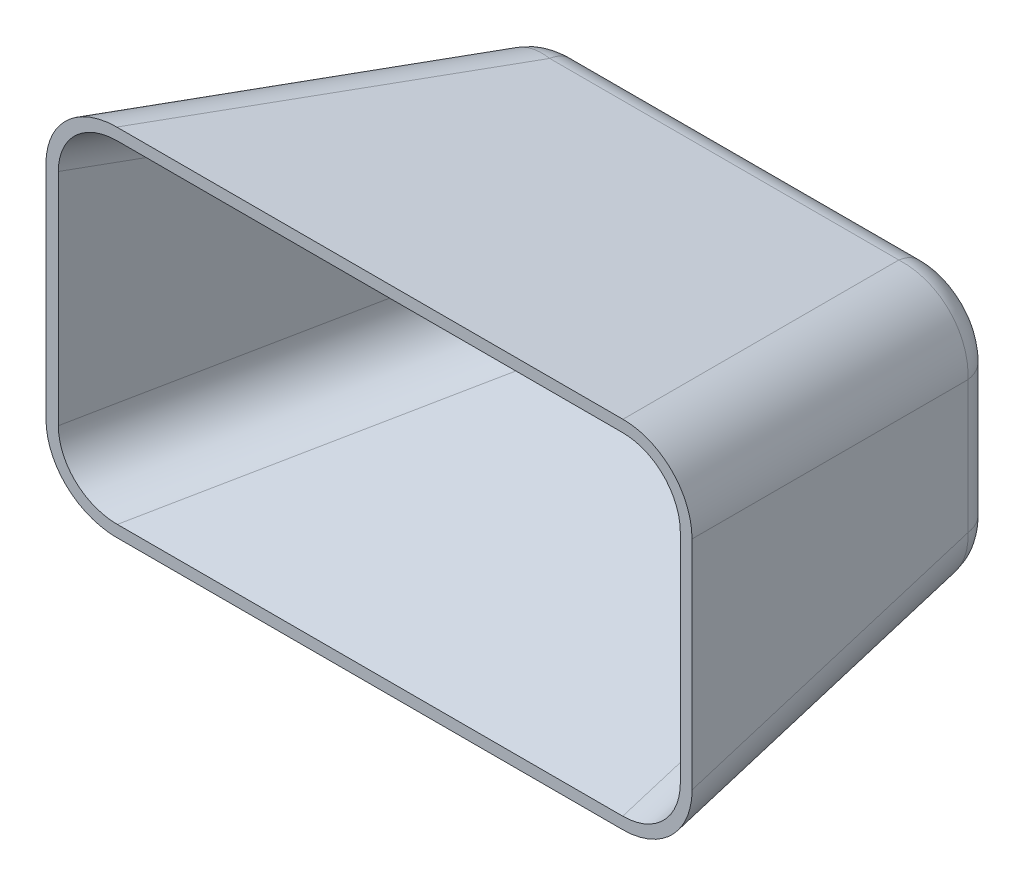
SolidWorks part; units mm, degrees
ref_plane "前视基准面" through (0, 0, 0) normal (0, 0, 1) x (1, 0, 0)
ref_plane "上视基准面" through (0, 0, 0) normal (0, 1, 0) x (1, 0, 0)
ref_plane "右视基准面" through (0, 0, 0) normal (1, 0, 0) x (0, 0, -1)
sketch "草图1" plane through (0, 0, 0) normal (0, 0, 1) x (1, 0, 0)
  line L5 (-139, 76.5) -> (139, 76.5)
  line L6 (-139, 76.5) -> (-139, -76.5)
  line L7 (-139, -76.5) -> (139, -76.5)
  line L8 (139, 76.5) -> (139, -76.5)
  line L9 (-139, 76.5) -> (139, -76.5) construction
  line L10 (-139, -76.5) -> (139, 76.5) construction
  line L15 (-85, -46.7806) -> (85, 46.7806) construction
  line L16 (-85, 46.7806) -> (85, -46.7806) construction
  point P0 (0, 0)
  point P6 (0, 0)
  dimension "D1" = 153
  dimension "D2" = 278
  dimension "D3" = 170
extrude "凸台-拉伸1" add sketch "草图1" along normal blind 150
ref_plane "基准面4" through (0, 0, 0) normal (0, 0, -1) x (-1, 0, 0)
sketch "草图2" plane through (0, 0, 0) normal (0, 0, -1) x (-1, 0, 0)
  line L0 (139, -76.5) -> (-139, -76.5) construction
  line L5 (-85, 76.5) -> (85, 76.5)
  line L6 (-85, 76.5) -> (-85, -76.5)
  line L7 (-139, 76.5) -> (139, 76.5)
  line L8 (-139, 76.5) -> (-139, -76.5)
  line L10 (139, 76.5) -> (139, -76.5)
  line L11 (-139, 76.5) -> (139, -76.5) construction
  line L12 (-139, -76.5) -> (139, 76.5) construction
  line L13 (-85, -76.5) -> (85, -76.5)
  line L14 (85, 76.5) -> (85, -76.5)
  line L15 (-85, 76.5) -> (85, -76.5) construction
  line L16 (-85, -76.5) -> (85, 76.5) construction
  line L18 (-139, 43.313) -> (139, 43.313)
  line L19 (-139, 43.313) -> (-139, -43.313)
  line L20 (-139, -43.313) -> (139, -43.313)
  line L21 (139, 43.313) -> (139, -43.313)
  line L22 (-139, 43.313) -> (139, -43.313) construction
  line L23 (-139, -43.313) -> (139, 43.313) construction
  point P0 (0, 0)
  point P8 (0, 0)
  dimension "D1" = 170
sketch "草图3" plane through (0, 76.5, 0) normal (0, 1, 0) x (1, 0, 0)
  line L0 (-85, 0) -> (-139, -150)
  line L1 (85, 0) -> (-85, 0) construction
  line L2 (85, 0) -> (-85, 0) construction
  line L3 (119, 0) -> (139, -150)
  line L4 (85, 0) -> (-85, 0) construction
  line L5 (139, -150) -> (139, 0)
  line L6 (139, 0) -> (-139, 0) construction
  line L7 (88.4129, 0) -> (-88.4129, 0) construction
  line L8 (139, 0) -> (119, 0)
  line L9 (-85, 0) -> (-139, 0)
  line L10 (-139, 0) -> (-139, -150)
  dimension "D1" = 20
sketch "草图4" plane through (139, 0, 0) normal (1, 0, 0) x (0, 0, -1)
  line L0 (0, 56.5) -> (-150, 76.5)
  line L1 (0, 43.313) -> (0, -43.313) construction
  line L2 (0, 76.5) -> (0, -76.5) construction
  line L3 (-150, 76.5) -> (0, 76.5)
  line L4 (0, 76.5) -> (0, 56.5)
  line L5 (0, -56.5) -> (-150, -76.5)
  line L6 (0, 76.5) -> (0, -76.5) construction
  line L7 (-150, -76.5) -> (0, -76.5)
  line L8 (0, -76.5) -> (0, -56.5)
  dimension "D1" = 20
  dimension "D2" = 20
extrude "切除-拉伸2" cut sketch "草图3" against normal through all
extrude "切除-拉伸3" cut sketch "草图4" against normal through all
fillet "圆角1" radius 30 4 edges at (129, -66.5, 75) (129, 66.5, 75) (-112, 66.5, 75) (-112, -66.5, 75)
fillet "圆角2" radius 15 8 edges at (-76.1603, 48.1092, 0) (-85, 0, 0) (-76.1603, -48.1092, 0) (17.3603, -56.5, 0) (110.3215, -47.8215, 0) (119, 0, 0) (110.3215, 47.8215, 0) (17.3603, 56.5, 0)
shell "抽壳3" thickness 5 removed face at (0.1304, 0, 150)
